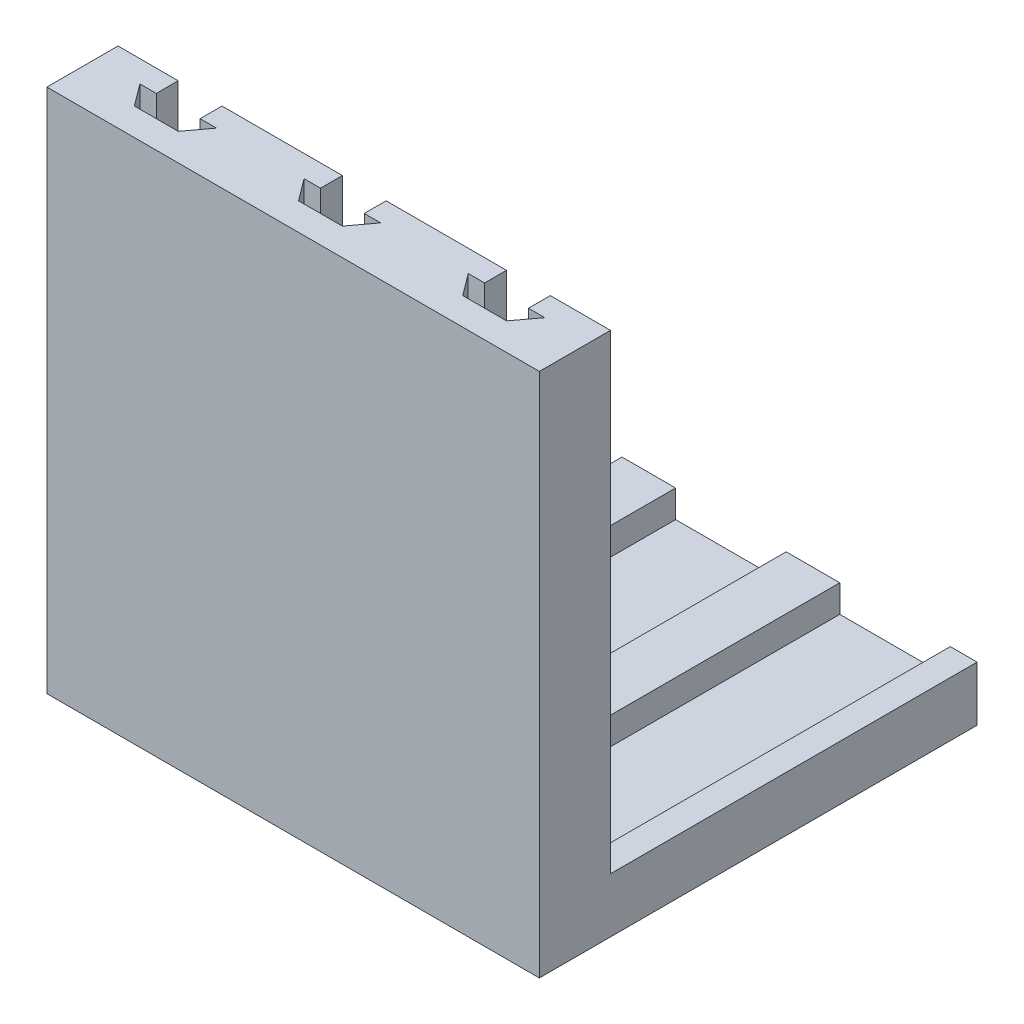
SolidWorks part; units mm, degrees
ref_plane "Front Plane" through (0, 0, 0) normal (0, 0, 1) x (1, 0, 0)
ref_plane "Top Plane" through (0, 0, 0) normal (0, 1, 0) x (1, 0, 0)
ref_plane "Right Plane" through (0, 0, 0) normal (1, 0, 0) x (0, 0, -1)
sketch "Sketch1" plane through (0, 0, 0) normal (0, 1, 0) x (1, 0, 0)
  line L1 (-15, -40) -> (15, -40)
  line L2 (-15, -40) -> (-15, 40)
  line L3 (-15, 40) -> (15, 40)
  line L4 (15, -40) -> (15, 40)
  line L5 (-15, -40) -> (15, 40) construction
  line L6 (-15, 40) -> (15, -40) construction
  point P0 (0, 0)
  dimension "D1" = 80
  dimension "D2" = 30
extrude "Boss-Extrude1" add sketch "Sketch1" along normal blind 10
sketch "Sketch2" plane through (0, 10, 0) normal (0, 1, 0) x (1, 0, 0)
  line L0 (15, -40) -> (15, 40) construction
  line L1 (-15, -40) -> (15, -40)
  line L2 (-15, -40) -> (-15, -27)
  line L3 (-15, -27) -> (15, -27)
  line L4 (15, -40) -> (15, -27)
  dimension "D1" = 13
extrude "Boss-Extrude2" add sketch "Sketch2" along normal blind 86 contours L3 L4 L1 L2
sketch "Sketch3" plane through (0, 96, 0) normal (0, 1, 0) x (1, 0, 0)
  line L0 (0, -27) -> (0, -40) construction
  line L1 (-15, -27) -> (15, -27) construction
  line L2 (-15, -40) -> (15, -40) construction
  line L3 (-4, -27) -> (4, -27)
  line L5 (-15, -27) -> (15, -27) construction
  line L6 (-4, -27) -> (-4, -31)
  line L7 (-4, -31) -> (-7, -31)
  line L8 (-7, -31) -> (-4, -35)
  line L9 (-4, -35) -> (4, -35)
  line L10 (4, -35) -> (7, -31)
  line L11 (7, -31) -> (4, -31)
  line L12 (4, -31) -> (4, -27)
  dimension "D1" = 8
  dimension "D2" = 4
  dimension "D3" = 4
  dimension "D4" = 3
extrude "Cut-Extrude1" cut sketch "Sketch3" against normal blind 40
sketch "Sketch4" plane through (0, 10, 0) normal (0, 1, 0) x (1, 0, 0)
  line L0 (0, 40) -> (0, -27) construction
  line L1 (15, 40) -> (-15, 40) construction
  line L2 (15, -27) -> (15, 40) construction
  line L3 (-15, -27) -> (15, -27) construction
  line L4 (-10.1, 40) -> (10.1, 40)
  line L5 (-10.1, 40) -> (-10.1, -27)
  line L7 (10.1, 40) -> (10.1, -27)
  line L8 (4, -27) -> (15, -27) construction
  line L10 (10.1, -27) -> (-10.1, -27)
  line L11 (-15, 40) -> (-15, -27) construction
  dimension "D1" = 20.2
  dimension "D2" = 4.9
extrude "Cut-Extrude2" cut sketch "Sketch4" against normal blind 5
sketch "Sketch5" plane through (0, 56, 0) normal (0, 1, 0) x (1, 0, 0)
  line L0 (0, -27) -> (0, -35) construction
  line L1 (4, -27) -> (-4, -27) construction
  line L2 (-4, -35) -> (4, -35) construction
  line L3 (4, -31) -> (4, -27) construction
  line L4 (-4, -27) -> (4, -27)
  line L5 (-4, -27) -> (-4, -29)
  line L6 (-4, -29) -> (4, -29)
  line L7 (4, -27) -> (4, -29)
  line L8 (-4, -27) -> (-4, -31) construction
  dimension "D1" = 2
extrude "Cut-Extrude3" cut sketch "Sketch5" against normal blind 51
pattern_linear "LPattern1" count 3 spacing 30 along (-1, 0, 0) of "Boss-Extrude1", "Boss-Extrude2", "Cut-Extrude1", "Cut-Extrude2", "Cut-Extrude3"
